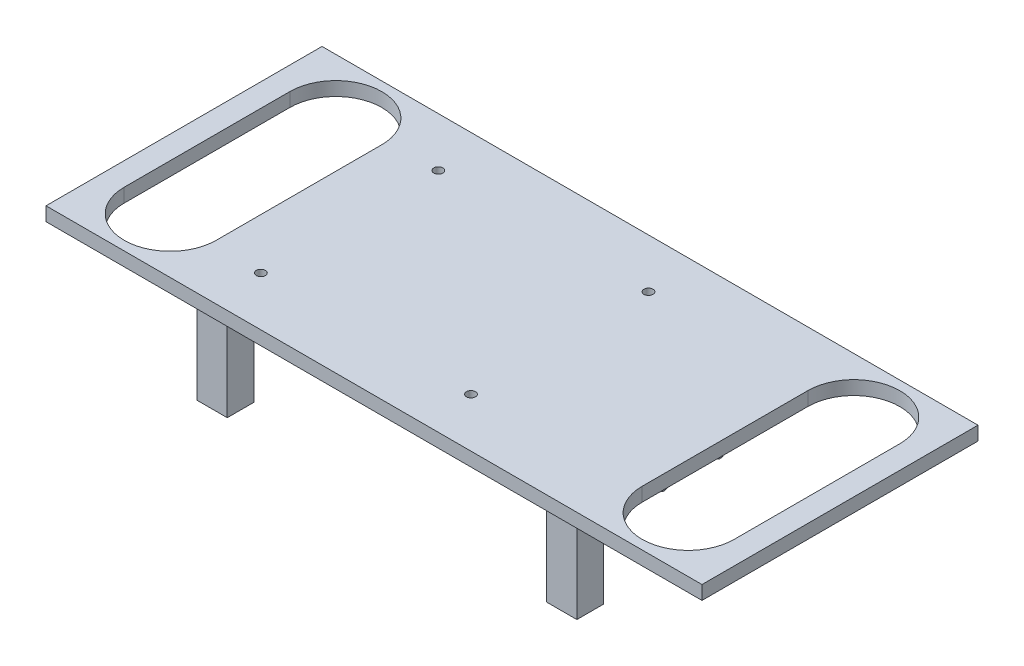
SolidWorks part; units mm, degrees
ref_plane "Front Plane" through (0, 0, 0) normal (0, 0, 1) x (1, 0, 0)
ref_plane "Top Plane" through (0, 0, 0) normal (0, 1, 0) x (1, 0, 0)
ref_plane "Right Plane" through (0, 0, 0) normal (1, 0, 0) x (0, 0, -1)
sketch "Sketch1" plane through (0, 0, 0) normal (0, 1, 0) x (1, 0, 0)
  line L0 (-5.842, 0) -> (-7.112, -1.2443)
  line L1 (-7.112, -1.2443) -> (-7.112, -8.6103)
  line L2 (-7.112, -8.6103) -> (1.27, -8.6103)
  line L3 (1.27, -8.6103) -> (1.27, -1.2443)
  line L4 (1.27, -1.2443) -> (0, 0)
  line L5 (0, 0) -> (-5.842, 0)
  line L6 (90.678, 0) -> (89.408, -1.2443)
  line L7 (89.408, -1.2443) -> (89.408, -8.6103)
  line L8 (89.408, -8.6103) -> (97.79, -8.6103)
  line L9 (97.79, -8.6103) -> (97.79, -1.2443)
  line L10 (97.79, -1.2443) -> (96.52, 0)
  line L11 (96.52, 0) -> (90.678, 0)
  point P2 (93.599, -8.6103)
  point P21 (-2.921, -8.6103)
  dimension "D1" = 7.366
  dimension "D2" = 8.382
  dimension "D3" = 1.778
  dimension "D4" = 5.842
  dimension "D5" = 96.52
extrude "Guide rods" add sketch "Sketch1" along normal blind 25.4
sketch "Sketch2" plane through (0, 25.4, 0) normal (0, 1, 0) x (1, 0, 0)
  line L0 (-7.112, -1.2443) -> (-7.112, -8.6103) construction
  line L1 (-45.212, -12.1663) -> (135.89, -12.1663)
  line L2 (-45.212, -12.1663) -> (-45.212, 64.0337)
  line L3 (-45.212, 64.0337) -> (135.89, 64.0337)
  line L4 (135.89, -12.1663) -> (135.89, 64.0337)
  line L5 (-7.112, -8.6103) -> (1.27, -8.6103) construction
  line L6 (97.79, -8.6103) -> (97.79, -1.2443) construction
  dimension "D1" = 38.1
  dimension "D2" = 3.556
  dimension "D3" = 38.1
  dimension "D4" = 76.2
extrude "baseplate" add sketch "Sketch2" along normal blind 3.81
sketch "Sketch4" plane through (0, 29.21, 0) normal (0, 1, 0) x (1, 0, 0)
  line L0 (-26.162, 48.7937) -> (-26.162, 3.0737) construction
  line L1 (-13.462, 48.7937) -> (-13.462, 3.0737)
  line L2 (-38.862, 48.7937) -> (-38.862, 3.0737)
  line L3 (-45.212, 64.0337) -> (-45.212, -12.1663) construction
  line L5 (-45.212, -12.1663) -> (135.89, -12.1663) construction
  line L6 (135.89, 64.0337) -> (-45.212, 64.0337) construction
  line L7 (45.339, 64.0337) -> (45.339, -12.1663) construction
  line L8 (116.84, 48.7937) -> (116.84, 3.0737) construction
  line L9 (104.14, 48.7937) -> (104.14, 3.0737)
  line L10 (129.54, 48.7937) -> (129.54, 3.0737)
  arc A0 (-13.462, 48.7937) -> (-38.862, 48.7937) centre (-26.162, 48.7937) ccw
  arc A1 (-38.862, 3.0737) -> (-13.462, 3.0737) centre (-26.162, 3.0737) ccw
  arc A2 (104.14, 48.7937) -> (129.54, 48.7937) centre (116.84, 48.7937) cw
  arc A3 (129.54, 3.0737) -> (104.14, 3.0737) centre (116.84, 3.0737) cw
  point P2 (-26.162, 25.9337)
  point P17 (116.84, 25.9337)
  dimension "D1" = 15.24
  dimension "D2" = 25.4
  dimension "D3" = 6.35
  dimension "D4" = 15.24
extrude "Handles" cut sketch "Sketch4" against normal through all
sketch "Sketch5" plane through (0, 29.21, 0) normal (0, 1, 0) x (1, 0, 0)
  line L0 (-45.212, 64.0337) -> (-45.212, -12.1663) construction
  line L5 (0.508, 50.4337) -> (0.508, 1.4337) construction
  circle A0 centre (0.508, 50.4337) radius 1.25
  circle A1 centre (0.508, 1.4337) radius 1.25
  circle A2 centre (58.508, 50.4337) radius 1.25
  circle A3 centre (58.508, 1.4337) radius 1.25
  point P10 (-45.212, 25.9337)
  point P12 (0.508, 25.9337)
  point P13 (0, 0)
  point P14 (0, 0)
  dimension "D3" = 2.5
  dimension "D1" = 58
  dimension "D2" = 49
  dimension "D5" = 45.72
extrude "Cut-Extrude1" cut sketch "Sketch5" against normal through all contours A2 | A3 | A0 | A1
sketch "Sketch6" plane through (135.89, 0, 0) normal (1, 0, 0) x (0, 0, -1)
  line L0 (24.511, 15.875) -> (17.526, 15.875) construction
  line L1 (0, 25.4) -> (0, 0) construction
  line L2 (-12.1663, 25.4) -> (64.0337, 25.4) construction
  line L4 (17.78, 25.4) -> (31.115, 25.4)
  line L6 (17.526, 15.875) -> (9.271, 25.4)
  line L7 (9.271, 25.4) -> (39.751, 25.4)
  line L8 (39.751, 25.4) -> (31.496, 15.875)
  arc A0 (31.496, 15.875) -> (17.526, 15.875) centre (24.511, 15.875) ccw
  point P1 (9.0414, 25.4)
  point P6 (24.511, 22.86)
  line M8 (-12.1663, 25.4) -> (64.0337, 25.4)
  dimension "D2" = 13.97
  dimension "D1" = 17.526
  dimension "D3" = 2.54
  dimension "D4" = 30.48
extrude "Boss-Extrude1" add sketch "Sketch6" against normal up to surface (149.352 mm away) from surface contours A0 L8 L6 M8 region at (135.89, 25.0807, -24.4475) up to face at (-13.462, 27.305, -25.9337) starting at face at (104.14, 27.305, -25.9337)
fillet "Fillet1" radius 1.27 2 edges at (45.339, 15.875, -17.526) (45.339, 15.875, -31.496)
sketch "Sketch7" plane through (0, 0, -64.0337) normal (0, 0, -1) x (-1, 0, 0)
  line L0 (-104.14, 17.4331) -> (13.462, 17.4331) construction
  line L1 (-104.14, 25.4) -> (-96.52, 25.4)
  line L2 (-104.14, 25.4) -> (-104.14, 17.4331)
  line L3 (-104.14, 17.4331) -> (-96.52, 17.4331)
  line L4 (-96.52, 25.4) -> (-96.52, 17.4331)
  line L5 (13.462, 25.4) -> (-104.14, 25.4) construction
  line L6 (13.462, 25.4) -> (5.842, 25.4)
  line L7 (13.462, 25.4) -> (13.462, 17.4331)
  line L8 (13.462, 17.4331) -> (5.842, 17.4331)
  line L9 (5.842, 25.4) -> (5.842, 17.4331)
  line L20 (-77.47, 25.4) -> (-13.208, 25.4)
  line L25 (-77.47, 25.4) -> (-77.47, 17.4331)
  line L26 (-77.47, 17.4331) -> (-13.208, 17.4331)
  line L27 (-13.208, 25.4) -> (-13.208, 17.4331)
  dimension "D1" = 7.62
  dimension "D2" = 19.05
  dimension "D3" = 19.05
extrude "Cut-Extrude2" cut sketch "Sketch7" against normal up to surface (64.0337 mm away) up to face at (93.599, 12.7, 0)
